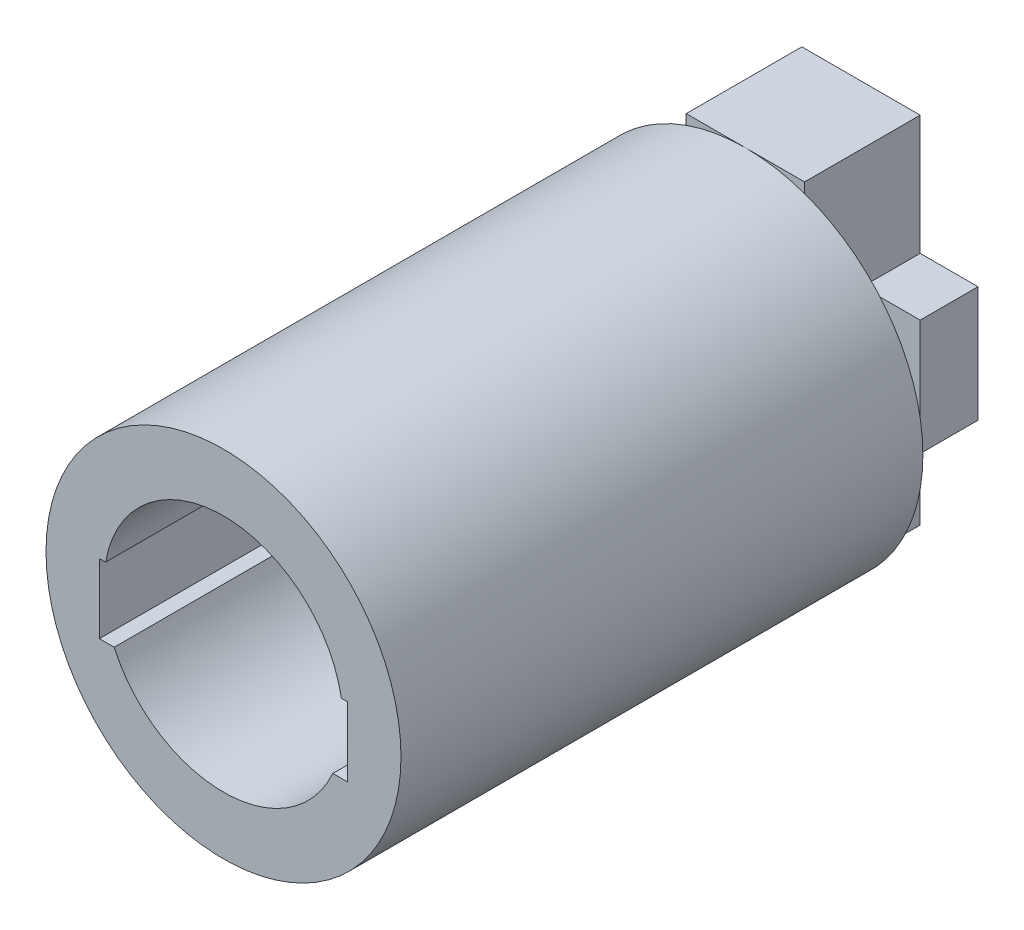
SolidWorks part; units mm, degrees
ref_plane "Front Plane" through (0, 0, 0) normal (0, 0, 1) x (1, 0, 0)
ref_plane "Top Plane" through (0, 0, 0) normal (0, 1, 0) x (1, 0, 0)
ref_plane "Right Plane" through (0, 0, 0) normal (1, 0, 0) x (0, 0, -1)
ref_plane "Plane6" through (0, 0, 0) normal (0, 0, 1) x (1, 0, 0)
sketch "Sketch9" plane through (0, 0, 0) normal (0, 0, 1) x (1, 0, 0)
  line L1 (21.0823, -4.604) -> (14.7423, -4.604) construction
  line L5 (14.6923, -3.704) -> (21.1323, -3.704)
  line L6 (14.6923, -3.704) -> (14.6923, -5.504)
  line L7 (14.6923, -5.504) -> (21.1323, -5.504)
  line L8 (21.1323, -3.704) -> (21.1323, -5.504)
  line L9 (21.0823, -5.454) -> (14.7423, -5.454) construction
  line L10 (17.9123, -5.454) -> (17.9123, -3.704) construction
  circle A0 centre (17.9123, -4.239) radius 4.605
  circle A1 centre (17.9123, -4.239) radius 3.105
  dimension "D1" = 6.21
  dimension "D8" = 1.5
  dimension "D3" = 0.9
  dimension "D4" = 0.9
  dimension "D6" = 3.22
  dimension "D7" = 3.22
ref_plane "Plane8" through (0, 0, -13.54) normal (0, 0, 1) x (1, 0, 0)
extrude "Boss-Extrude6" add sketch "Sketch9" against normal up to surface (13.54 mm away) contours A0 A1 L5 L8 L7 L6 region at (13.4375, -4.239, 0) up to plane "Plane8"
sketch "Sketch11" plane through (0, 0, -13.54) normal (0, 0, 1) x (1, 0, 0)
  line L1 (16.3773, -8.844) -> (19.4473, -8.844)
  line L2 (16.3773, -8.844) -> (16.3773, 0.366)
  line L3 (16.3773, 0.366) -> (19.4473, 0.366)
  line L4 (19.4473, -8.844) -> (19.4473, 0.366)
  line L5 (16.3773, -8.844) -> (19.4473, 0.366) construction
  line L6 (16.3773, 0.366) -> (19.4473, -8.844) construction
  line L8 (14.8773, -5.739) -> (20.9473, -5.739)
  line L9 (14.8773, -5.739) -> (14.8773, -2.739)
  line L10 (14.8773, -2.739) -> (20.9473, -2.739)
  line L11 (20.9473, -5.739) -> (20.9473, -2.739)
  line L12 (14.8773, -5.739) -> (20.9473, -2.739) construction
  line L13 (14.8773, -2.739) -> (20.9473, -5.739) construction
  point P0 (17.9123, -4.239)
  point P8 (0, 0)
  point P9 (17.9123, -4.239)
  point P14 (0, 0)
  dimension "D1" = 3.07
  dimension "D2" = 3
  dimension "D3" = 1.5
extrude "Boss-Extrude7" add sketch "Sketch11" against normal blind 3 contours L2 L3 L4 L1
ref_plane "Plane9" through (0, 0, -16.54) normal (0, 0, -1) x (-1, 0, 0)
extrude "Boss-Extrude8" add sketch "Sketch11<7>" along normal blind 1.5 from surface contours L8 L11 L10 L4 | L10 L9 L8 L2 region at (15.6273, -4.239, -13.54) region at (20.1973, -4.239, -13.54) starting at plane "Plane9"
sketch "Sketch11<7>" plane through (0, 0, -13.54) normal (0, 0, 1) x (1, 0, 0) same geometry as "Sketch11"
